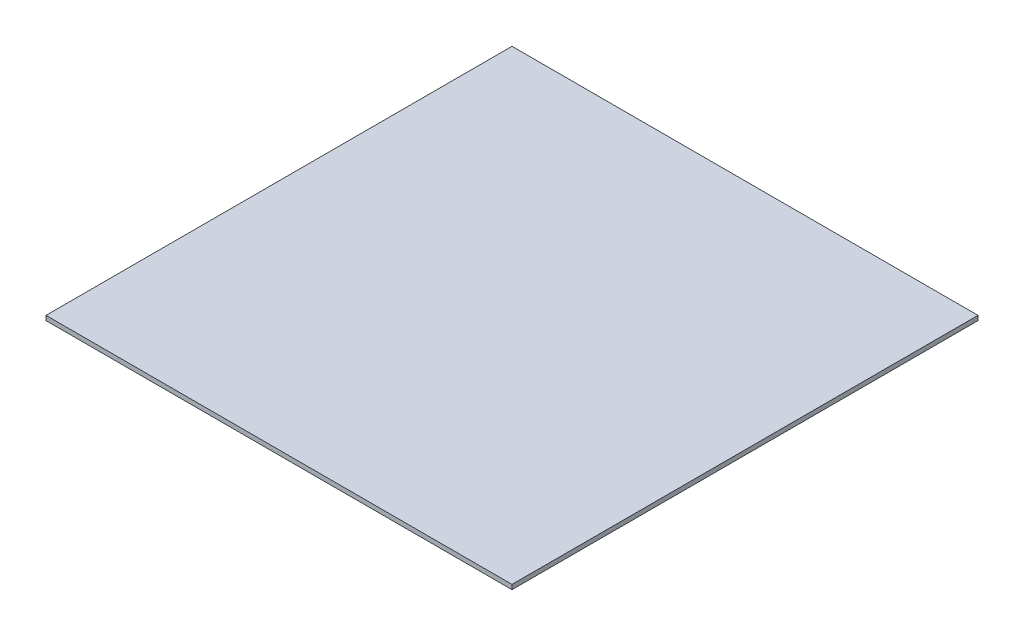
SolidWorks part; units mm, degrees
ref_plane "Front Plane" through (0, 0, 0) normal (0, 0, 1) x (1, 0, 0)
ref_plane "Top Plane" through (0, 0, 0) normal (0, 1, 0) x (1, 0, 0)
ref_plane "Right Plane" through (0, 0, 0) normal (1, 0, 0) x (0, 0, -1)
sketch "Sketch1" plane through (0, 0, 0) normal (0, 1, 0) x (1, 0, 0)
  line L1 (-152.4, 152.4) -> (152.4, 152.4)
  line L2 (-152.4, 152.4) -> (-152.4, -152.4)
  line L3 (-152.4, -152.4) -> (152.4, -152.4)
  line L4 (152.4, 152.4) -> (152.4, -152.4)
  line L5 (-152.4, 152.4) -> (152.4, -152.4) construction
  line L6 (-152.4, -152.4) -> (152.4, 152.4) construction
  point P0 (0, 0)
  dimension "D1" = 304.8
extrude "Boss-Extrude1" add sketch "Sketch1" along normal blind 3
